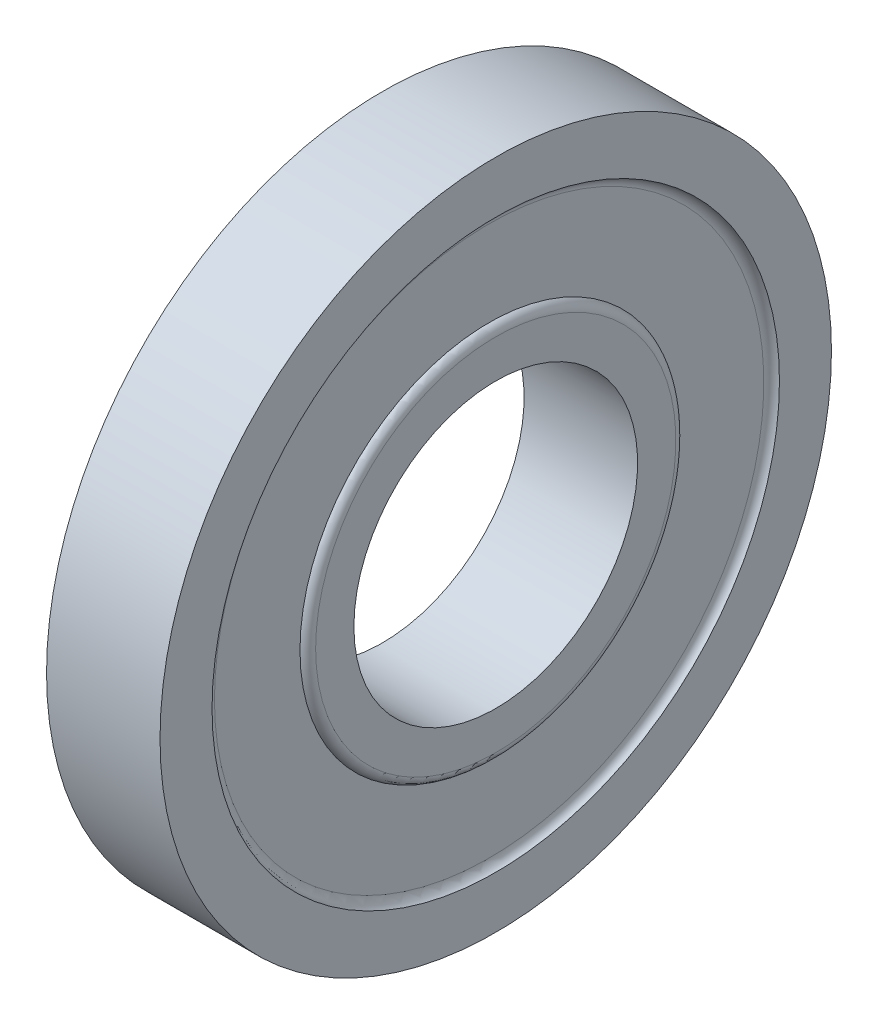
SolidWorks part; units mm, degrees
material "Malleable Cast Iron"
ref_plane "Front Plane" through (0, 0, 0) normal (0, 0, 1) x (1, 0, 0)
ref_plane "Top Plane" through (0, 0, 0) normal (0, 1, 0) x (1, 0, 0)
ref_plane "Right Plane" through (0, 0, 0) normal (1, 0, 0) x (0, 0, -1)
sketch "Sketch3" plane through (0, 0, 0) normal (0, 0, 1) x (1, 0, 0)
  line L0 (-14.5406, 0) -> (16.0536, 0) construction
  line L1 (6, 15) -> (-6, 15)
  line L2 (-6, 15) -> (-6, 20)
  line L3 (-6, 20) -> (-5.3, 20)
  line L4 (-5.3, 20) -> (-5.3, 30)
  line L5 (-5.3, 30) -> (-6, 30)
  line L6 (-6, 30) -> (-6, 35.5)
  line L7 (-6, 35.5) -> (6, 35.5)
  line L9 (6, 30) -> (6, 35.5)
  line L10 (5.3, 30) -> (6, 30)
  line L11 (5.3, 20) -> (5.3, 30)
  line L12 (6, 20) -> (5.3, 20)
  line L13 (6, 15) -> (6, 20)
  line L14 (0, 15) -> (0, 0) construction
  point P11 (5.65, 20)
  point P17 (-5.65, 20)
  dimension "D1" = 15
  dimension "D2" = 35.5
  dimension "D3" = 20
  dimension "D4" = 30
  dimension "D5" = 12
  dimension "D6" = 12
  dimension "D7" = 10.6
revolve "Revolve1" add sketch "Sketch3" angle 360 about L0
fillet "Fillet1" radius 1 4 edges at (6, 0, 20) (5.3, 0, 30) (-5.3, 0, 30) (-6, 0, 20)
